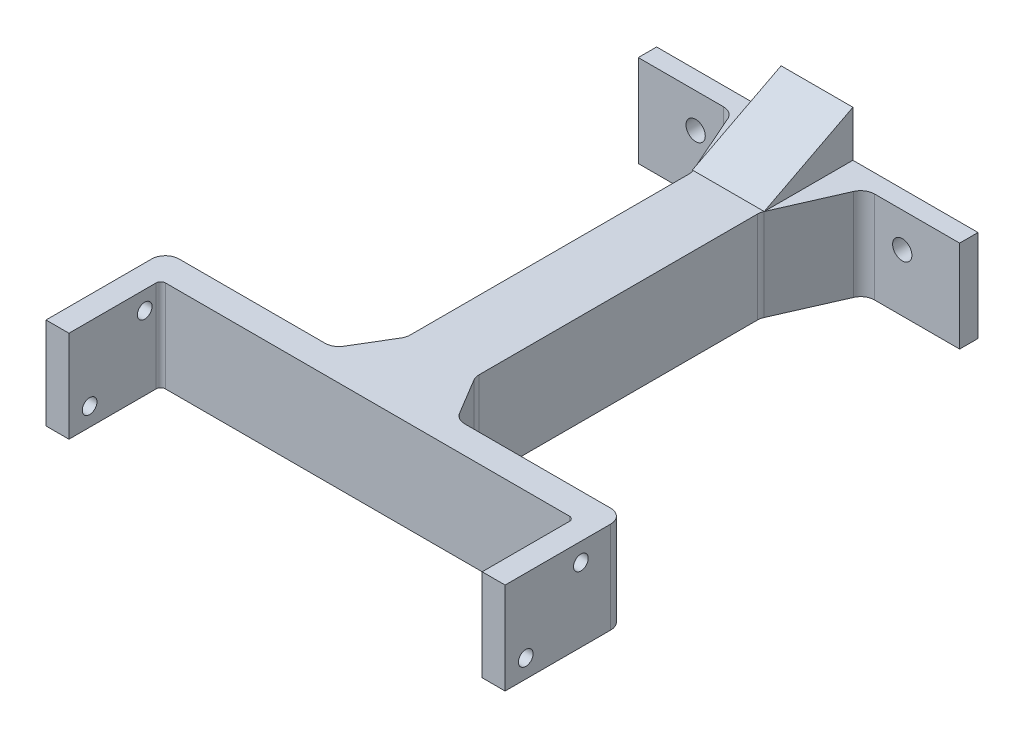
SolidWorks part; units mm, degrees
ref_plane "前视基准面" through (0, 0, 0) normal (0, 0, 1) x (1, 0, 0)
ref_plane "上视基准面" through (0, 0, 0) normal (0, 1, 0) x (1, 0, 0)
ref_plane "右视基准面" through (0, 0, 0) normal (1, 0, 0) x (0, 0, -1)
sketch "草图1" plane through (0, 0, 0) normal (0, 0, 1) x (1, 0, 0)
  line L1 (-27.1107, 16.6861) -> (42.8893, 16.6861)
  line L2 (-27.1107, 16.6861) -> (-27.1107, -3.3139)
  line L3 (-27.1107, -3.3139) -> (42.8893, -3.3139)
  line L4 (42.8893, 16.6861) -> (42.8893, -3.3139)
  dimension "D1" = 70
  dimension "D2" = 20
extrude "凸台-拉伸1" add sketch "草图1" along normal blind 4
sketch "草图2" plane through (0, 0, 4) normal (0, 0, 1) x (1, 0, 0)
  line L0 (42.8893, 16.6861) -> (-27.1107, 16.6861) construction
  line L1 (-27.1107, 16.6861) -> (-27.1107, -3.3139) construction
  line L2 (42.8893, -3.3139) -> (42.8893, 16.6861) construction
  circle A0 centre (-14.6107, 9.1861) radius 2.1
  circle A1 centre (30.3893, 9.1861) radius 2.1
  dimension "D1" = 7.5
  dimension "D2" = 7.5
  dimension "D3" = 12.5
  dimension "D4" = 12.5
  dimension "D5" = 4.2
  dimension "D6" = 4.2
extrude "切除-拉伸1" cut sketch "草图2" against normal blind 4
sketch "草图3" plane through (0, 0, 4) normal (0, 0, 1) x (1, 0, 0)
  line L0 (42.8893, 16.6861) -> (-27.1107, 16.6861) construction
  line L1 (0.3893, 16.6861) -> (15.3893, 16.6861)
  line L2 (0.3893, 16.6861) -> (0.3893, -3.3139)
  line L3 (0.3893, -3.3139) -> (15.3893, -3.3139)
  line L4 (15.3893, 16.6861) -> (15.3893, -3.3139)
  line L5 (-27.1107, -3.3139) -> (42.8893, -3.3139) construction
  line L6 (-27.1107, 16.6861) -> (-27.1107, -3.3139) construction
  dimension "D1" = 15
  dimension "D2" = 27.5
extrude "凸台-拉伸2" add sketch "草图3" along normal blind 88
sketch "草图4" plane through (0, 0, 92) normal (0, 0, 1) x (1, 0, 0)
  line L0 (0.3893, 16.6861) -> (-27.1107, 16.6861) construction
  line L1 (-42.1107, 16.6861) -> (57.8893, 16.6861)
  line L2 (-42.1107, 16.6861) -> (-42.1107, -3.3139)
  line L3 (-42.1107, -3.3139) -> (57.8893, -3.3139)
  line L4 (57.8893, 16.6861) -> (57.8893, -3.3139)
  line L5 (15.3893, -3.3139) -> (42.8893, -3.3139) construction
  line L6 (0.3893, 16.6861) -> (0.3893, -3.3139) construction
  dimension "D1" = 100
  dimension "D2" = 42.5
extrude "凸台-拉伸3" add sketch "草图4" along normal blind 6
sketch "草图5" plane through (0, 0, 98) normal (0, 0, 1) x (1, 0, 0)
  line L0 (-42.1107, -3.3139) -> (57.8893, -3.3139) construction
  line L1 (-42.1107, 16.6861) -> (-37.1107, 16.6861)
  line L2 (-42.1107, 16.6861) -> (-42.1107, -3.3139)
  line L3 (-42.1107, -3.3139) -> (-37.1107, -3.3139)
  line L4 (-37.1107, 16.6861) -> (-37.1107, -3.3139)
  line L5 (57.8893, 16.6861) -> (-42.1107, 16.6861) construction
  line L6 (57.8893, 16.6861) -> (52.8893, 16.6861)
  line L7 (57.8893, 16.6861) -> (57.8893, -3.3139)
  line L8 (57.8893, -3.3139) -> (52.8893, -3.3139)
  line L9 (52.8893, 16.6861) -> (52.8893, -3.3139)
  line L10 (57.8893, -3.3139) -> (57.8893, 16.6861) construction
  dimension "D1" = 5
  dimension "D2" = 5
extrude "凸台-拉伸4" add sketch "草图5" along normal blind 20
sketch "草图6" plane through (-37.1107, 0, 0) normal (1, 0, 0) x (0, 0, -1)
  line L0 (-118, 16.6861) -> (-92, 16.6861) construction
  line L1 (-118, -3.3139) -> (-92, -3.3139) construction
  line L2 (-118, -3.3139) -> (-118, 16.6861) construction
  circle A0 centre (-101.5, 12.6861) radius 1.6
  circle A1 centre (-113.5, 0.6861) radius 1.6
  dimension "D1" = 3.2
  dimension "D2" = 3.2
  dimension "D3" = 4
  dimension "D4" = 4
  dimension "D5" = 12
  dimension "D6" = 4.5
extrude "切除-拉伸2" cut sketch "草图6" along normal up to surface (95 mm away) up to face at (57.8893, 6.6861, 105)
extrude "切除-拉伸3" cut sketch "草图6<2>" against normal blind 20
sketch "草图6<2>" plane through (-37.1107, 0, 0) normal (1, 0, 0) x (0, 0, -1) same geometry as "草图6"
sketch "草图7" plane through (0, -3.3139, 0) normal (0, -1, 0) x (1, 0, 0)
  line L0 (0.3893, 4) -> (0.3893, 19.9004)
  line L1 (0.3893, 92) -> (0.3893, 4) construction
  line L2 (0.3893, 19.9004) -> (-6.6107, 4)
  line L3 (-27.1107, 4) -> (0.3893, 4) construction
  line L4 (-6.6107, 4) -> (0.3893, 4)
  line L5 (15.3893, 4) -> (22.3893, 4)
  line L6 (15.3893, 4) -> (42.8893, 4) construction
  line L7 (22.3893, 4) -> (15.3893, 19.9004)
  line L8 (15.3893, 92) -> (15.3893, 4) construction
  line L9 (15.3893, 19.9004) -> (15.3893, 4)
  dimension "D1" = 7
  dimension "D2" = 7
extrude "凸台-拉伸5" add sketch "草图7" against normal blind 20
sketch "草图8" plane through (0, -3.3139, 0) normal (0, -1, 0) x (1, 0, 0)
  line L0 (-5.6107, 92) -> (0.3893, 82)
  line L1 (-42.1107, 92) -> (0.3893, 92) construction
  line L2 (0.3893, 92) -> (0.3893, 19.9004) construction
  line L3 (0.3893, 82) -> (0.3893, 92)
  line L4 (0.3893, 92) -> (-5.6107, 92)
  line L5 (15.3893, 82) -> (15.3893, 92)
  line L6 (15.3893, 92) -> (15.3893, 19.9004) construction
  line L7 (15.3893, 92) -> (21.3893, 92)
  line L8 (15.3893, 92) -> (57.8893, 92) construction
  line L9 (21.3893, 92) -> (15.3893, 82)
  dimension "D1" = 10
  dimension "D2" = 10
  dimension "D3" = 6
  dimension "D4" = 6
extrude "凸台-拉伸6" add sketch "草图8" against normal blind 20
fillet "圆角1" radius 3 10 edges at (-42.1107, 6.6861, 92) (57.8893, 6.6861, 92) (0.3893, 6.6861, 19.9004) (-6.6107, 6.6861, 4) (22.3893, 6.6861, 4) (15.3893, 6.6861, 19.9004) (21.3893, 6.6861, 92) (15.3893, 6.6861, 82) (0.3893, 6.6861, 82) (-5.6107, 6.6861, 92)
fillet "圆角2" radius 1 2 edges at (-37.1107, 6.6861, 98) (52.8893, 6.6861, 98)
sketch "草图9" plane through (0, 16.6861, 0) normal (0, 1, 0) x (1, 0, 0)
  line L1 (15.6436, -19.3228) -> (0, -19.3228)
  line L2 (15.6436, -19.3228) -> (15.6436, 0)
  line L3 (15.6436, 0) -> (0, 0)
  line L4 (0, -19.3228) -> (0, 0)
extrude "凸台-拉伸7" add sketch "草图9" along normal blind 10
sketch "草图10" plane through (15.6436, 0, 0) normal (1, 0, 0) x (0, 0, -1)
  line L0 (-19.3228, 16.6861) -> (0, 26.6861)
  line L1 (-19.3228, 26.6861) -> (-19.3228, 16.6861) construction
  line L2 (0, 26.6861) -> (-19.3228, 26.6861)
  line L3 (-19.3228, 26.6861) -> (-19.3228, 16.6861)
extrude "切除-拉伸4" cut sketch "草图10" against normal up to next
equation "\"、\"=130"
